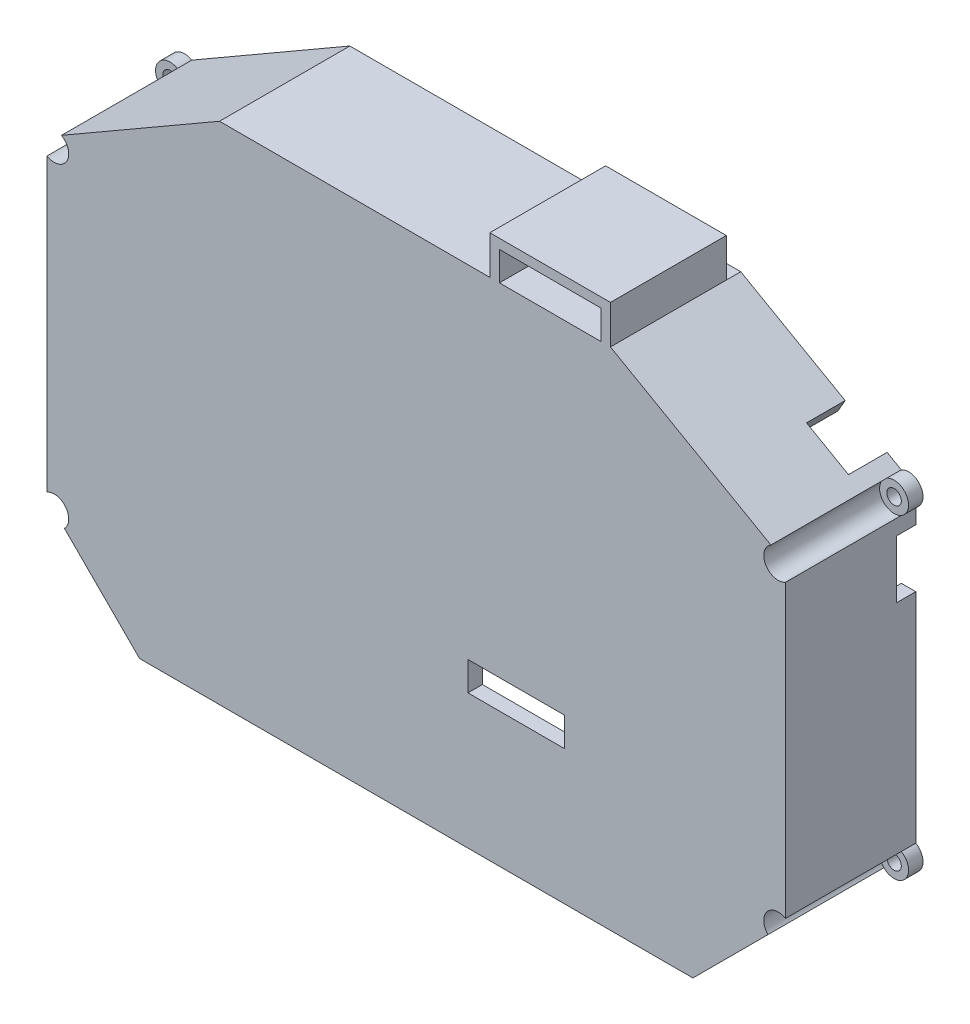
SolidWorks part; units mm, degrees
ref_plane "Front" through (0, 0, 0) normal (0, 0, 1) x (1, 0, 0)
ref_plane "Top" through (0, 0, 0) normal (0, 1, 0) x (1, 0, 0)
ref_plane "Right" through (0, 0, 0) normal (1, 0, 0) x (0, 0, -1)
sketch "草图2" plane through (0, 0, 0) normal (0, 0, 1) x (1, 0, 0)
  line L1 (73.4834, 35.3384) -> (40.2385, 54.25)
  line L2 (-76.5, 30.1519) -> (-76.5, -30.1519)
  line L4 (76.5, 30.1519) -> (76.5, -30.1519)
  line L5 (-75, 32.75) -> (75, -32.75) construction
  line L6 (-75, -32.75) -> (75, 32.75) construction
  line L7 (-40.7609, 54.25) -> (40.2385, 54.25)
  line L8 (75.75, 34.049) -> (75.7333, 34.0585)
  line L10 (-57.32, -50.43) -> (57.32, -50.43)
  line L11 (72.8787, -34.8713) -> (57.32, -50.43)
  line L12 (-72.8787, -34.8713) -> (-57.32, -50.43)
  line L13 (-73.5, 35.3481) -> (-40.7609, 54.25)
  circle A0 centre (-75, 32.75) radius 1.5
  circle A1 centre (75, 32.75) radius 1.5
  circle A2 centre (75, -32.75) radius 1.5
  circle A3 centre (-75, -32.75) radius 1.5
  arc A4 (-73.5, 35.3481) -> (-76.5, 30.1519) centre (-75, 32.75) ccw
  arc A5 (76.5, 30.1519) -> (73.4834, 35.3384) centre (75, 32.75) ccw
  arc A6 (72.8787, -34.8713) -> (76.5, -30.1519) centre (75, -32.75) ccw
  arc A7 (-76.5, -30.1519) -> (-72.8787, -34.8713) centre (-75, -32.75) ccw
  point P0 (0, 0)
extrude "凸台-拉伸1" add sketch "草图2" along normal blind 27 contours L2 A7 L12 L10 L11 A6 L4 A5 L1 L7 L13 A4 A0 A1 A2 A3 region at (-0.0184, 0.7527, 0)
shell "抽壳1" thickness 3 removed face at (-73.5, 32.75, 0)
sketch "草图3" plane through (0, 0, 27) normal (0, 0, 1) x (1, 0, 0)
  circle A0 centre (75, 32.75) radius 3
  circle A1 centre (75, -32.75) radius 3
  circle A2 centre (-75, -32.75) radius 3
  circle A3 centre (-75, 32.75) radius 3
extrude "切除-拉伸1" cut sketch "草图3" against normal blind 24
sketch "草图5" plane through (0, 0, 27) normal (0, 0, 1) x (1, 0, 0)
  line L1 (10.7074, -16.5771) -> (30.7074, -16.5771)
  line L2 (10.7074, -16.5771) -> (10.7074, -22.5771)
  line L3 (10.7074, -22.5771) -> (30.7074, -22.5771)
  line L4 (30.7074, -16.5771) -> (30.7074, -22.5771)
  line L5 (10.7074, -16.5771) -> (30.7074, -22.5771) construction
  line L6 (10.7074, -22.5771) -> (30.7074, -16.5771) construction
  point P0 (20.7074, -19.5771)
extrude "切除-拉伸3" cut sketch "草图5" against normal blind 32
sketch "草图6" plane through (76.5, 0, 0) normal (1, 0, 0) x (0, 0, -1)
  line L0 (0, 26.9774) -> (-4, 26.9774)
  line L1 (0, 30.1519) -> (0, -30.1519) construction
  line L2 (-4, 26.9774) -> (-4, 14.9774)
  line L3 (-4, 14.9774) -> (0, 14.9774)
  line L4 (0, 14.9774) -> (0, 26.9774)
extrude "切除-拉伸4" cut sketch "草图6" against normal blind 32
sketch "草图7" plane through (33.1533, 58.2805, 0) normal (0.4945, 0.8692, 0) x (0.8692, -0.4945, 0)
  line L0 (43.0325, 0) -> (43.0325, -8)
  line L1 (46.3989, 0) -> (8.1514, 0) construction
  line L2 (43.0325, -8) -> (33.0325, -8)
  line L3 (33.0325, -8) -> (33.0325, 0)
  line L4 (33.0325, 0) -> (43.0325, 0)
extrude "切除-拉伸5" cut sketch "草图7" against normal blind 32
sketch "草图8" plane through (0, 0, 27) normal (0, 0, 1) x (1, 0, 0)
  line L0 (40.2385, 54.25) -> (40.2385, 62.25)
  line L1 (40.2385, 62.25) -> (15.2385, 62.25)
  line L2 (15.2385, 62.25) -> (15.2385, 54.25)
  line L3 (-40.7609, 54.25) -> (40.2385, 54.25) construction
  line L4 (15.2385, 54.25) -> (17.2385, 54.25)
  line L5 (17.2385, 54.25) -> (17.2385, 60.25)
  line L6 (17.2385, 60.25) -> (38.2385, 60.25)
  line L7 (38.2385, 60.25) -> (38.2385, 54.25)
  line L8 (38.2385, 54.25) -> (40.2385, 54.25)
extrude "凸台-拉伸2" add sketch "草图8" against normal blind 24
sketch "草图9" plane through (0, 54.25, 0) normal (0, 1, 0) x (1, 0, 0)
  line L0 (22.7385, -3) -> (32.7385, -3)
  line L1 (-40.7609, 0) -> (40.2385, 0) construction
  line L3 (22.7385, -3) -> (22.7385, 0)
  line L4 (22.7385, 0) -> (32.7385, 0)
  line L5 (32.7385, -3) -> (32.7385, 0)
  line L6 (27.7385, -3) -> (32.7385, 0) construction
  line L7 (22.7385, 0) -> (27.7385, -3) construction
  point P4 (27.7385, -3)
extrude "切除-拉伸6" cut sketch "草图9" against normal blind 24
sketch "草图10" plane through (0, -50.43, 0) normal (0, -1, 0) x (1, 0, 0)
  circle A1 centre (-18.75, 20) radius 1.35
  circle A2 centre (18.75, 20) radius 1.35
extrude "切除-拉伸7" cut sketch "草图10" against normal blind 10
sketch "草图11" plane through (0, -50.43, 0) normal (0, -1, 0) x (1, 0, 0)
  line L1 (-57.32, 0) -> (57.32, 0) construction
  line L2 (0, 3) -> (2, 3)
  line L3 (2, 3) -> (2, 0)
  line L4 (2, 0) -> (-2, 0)
  line L5 (-2, 0) -> (-2, 3)
  line L6 (-2, 3) -> (0, 3)
extrude "切除-拉伸8" cut sketch "草图11" against normal blind 10
